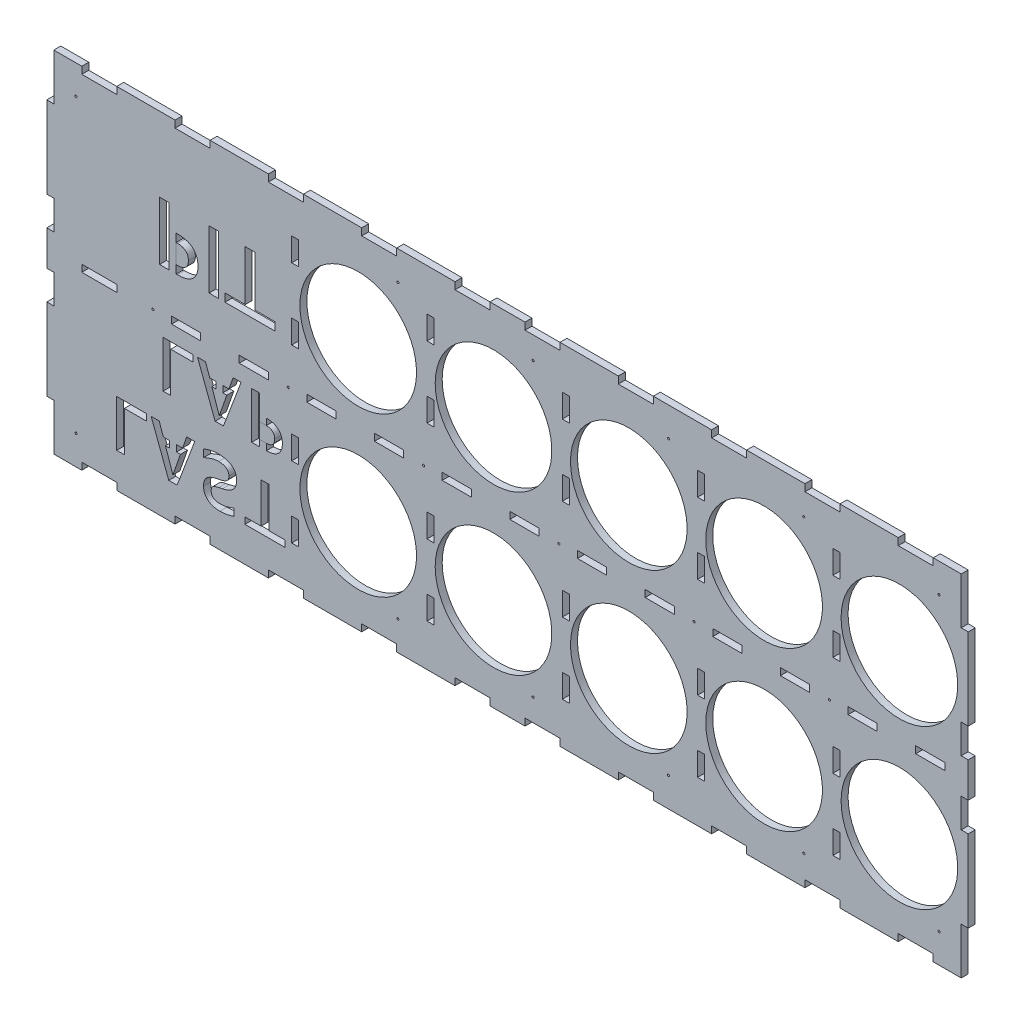
SolidWorks part; units mm, degrees
material "Acrylic (Medium-high impact)"
ref_plane "Front Plane" through (0, 0, 0) normal (0, 0, 1) x (1, 0, 0)
ref_plane "Top Plane" through (0, 0, 0) normal (0, 1, 0) x (1, 0, 0)
ref_plane "Right Plane" through (0, 0, 0) normal (1, 0, 0) x (0, 0, -1)
sketch "Sketch1" plane through (0, 0, 0) normal (0, 0, 1) x (1, 0, 0)
  line L1 (395, 150) -> (-395, 150)
  line L2 (395, 150) -> (395, -150)
  line L3 (395, -150) -> (-395, -150)
  line L4 (-395, 150) -> (-395, -150)
  line L5 (395, 150) -> (-395, -150) construction
  line L6 (395, -150) -> (-395, 150) construction
  point P0 (0, 0)
  dimension "D1" = 790
  dimension "D2" = 300
extrude "Boss-Extrude1" add sketch "Sketch1" along normal blind 6
sketch "Sketch2" plane through (0, 0, 0) normal (0, 0, -1) x (-1, 0, 0)
  line L0 (364.5528, -80.2188) -> (191, -80.2188) construction
  line L2 (191, -133) -> (191, -7) construction
  line L3 (304.6049, 86.1379) -> (205.3374, 86.1379) construction
  circle A0 centre (-336, -70) radius 50
  circle A1 centre (-220, -70) radius 50
  circle A2 centre (-220, 66) radius 50
  circle A3 centre (-336, 66) radius 50
  circle A4 centre (-104, -70) radius 50
  circle A5 centre (-104, 66) radius 50
  circle A6 centre (12, -70) radius 50
  circle A7 centre (12, 66) radius 50
  circle A8 centre (128, -70) radius 50
  circle A9 centre (128, 66) radius 50
  text T0 "<b>LAST</b>\r\n<b>LAP</b>" font "SOLIDWORKS GDT" height 40
  text T1 "<b>PIT</b>" font "SOLIDWORKS GDT" height 50
  point P0 (-336, 66)
  point P2 (-336, -70)
  point P4 (-220, 66)
  point P6 (-220, -70)
  dimension "D1" = 100
  dimension "D2" = 5
extrude "Cut-Extrude1" cut sketch "Sketch2" against normal blind 10
sketch "Sketch3" plane through (0, 0, 0) normal (0, 0, -1) x (-1, 0, 0)
  line L0 (286.8584, -120.2188) -> (286.8584, -77.9983) construction
  line L1 (290.4225, -120.2188) -> (283.2943, -120.2188) construction
  line L2 (247.1116, -56.4213) -> (247.1116, -7.6896) construction
  line L3 (250.6756, -56.4213) -> (243.5475, -56.4213) construction
  line L4 (290.0479, 66.5177) -> (290.0479, 86.1379) construction
  line L5 (283.8584, -100.0307) -> (289.8584, -100.0307)
  line L6 (283.8584, -100.0307) -> (283.8584, -87.3624)
  line L7 (283.8584, -87.3624) -> (289.8584, -87.3624)
  line L8 (289.8584, -100.0307) -> (289.8584, -87.3624)
  line L9 (283.8584, -100.0307) -> (289.8584, -87.3624) construction
  line L10 (283.8584, -87.3624) -> (289.8584, -100.0307) construction
  line L11 (244.1116, -36.3269) -> (250.1116, -36.3269)
  line L12 (244.1116, -36.3269) -> (244.1116, -13.8977)
  line L13 (244.1116, -13.8977) -> (250.1116, -13.8977)
  line L14 (250.1116, -36.3269) -> (250.1116, -13.8977)
  line L15 (244.1116, -36.3269) -> (250.1116, -13.8977) construction
  line L16 (244.1116, -13.8977) -> (250.1116, -36.3269) construction
  line L17 (290.0479, 81.5454) -> (284.0479, 81.5454)
  line L18 (290.0479, 81.5454) -> (290.0479, 32.0485)
  line L19 (290.0479, 32.0485) -> (284.0479, 32.0485)
  line L20 (284.0479, 81.5454) -> (284.0479, 32.0485)
  line L21 (212.7722, -32.1175) -> (212.7722, -16.4213) construction
  line L22 (212.7722, -27.2579) -> (206.7722, -27.2579)
  line L23 (212.7722, -27.2579) -> (212.7722, -59.8105)
  line L24 (212.7722, -59.8105) -> (206.7722, -59.8105)
  line L25 (206.7722, -27.2579) -> (206.7722, -59.8105)
  point P8 (286.8584, -93.6965)
  point P13 (247.1116, -25.1123)
  dimension "D1" = 6
extrude "Boss-Extrude2" add sketch "Sketch3" against normal up to surface (6 mm away)
sketch "Sketch4" plane through (0, 0, 0) normal (0, 0, -1) x (-1, 0, 0)
  line L0 (-395, -150) -> (-395, 150) construction
  line L1 (-395, -150) -> (-389, -150)
  line L2 (-395, -150) -> (-395, -110)
  line L3 (-395, -110) -> (-389, -110)
  line L4 (-389, -150) -> (-389, -110)
  line L5 (-395, 150) -> (395, 150) construction
  line L6 (-395, -40) -> (-389, -40)
  line L7 (-395, -40) -> (-395, -15)
  line L8 (-389, -15) -> (-395, -15)
  line L9 (-389, -40) -> (-389, -15)
  line L10 (-45, 150) -> (-45, 144)
  line L11 (0, 76.0027) -> (0, 0) construction
  line L12 (0, 0) -> (-103.2, 0) construction
  line L13 (-389, 40) -> (-389, 15)
  line L14 (-389, 15) -> (-395, 15)
  line L15 (-395, 40) -> (-395, 15)
  line L16 (-395, 40) -> (-389, 40)
  line L17 (-389, 150) -> (-389, 110)
  line L18 (-45, 150) -> (-15, 150)
  line L19 (-395, 110) -> (-389, 110)
  line L20 (-45, 144) -> (-15, 144)
  line L21 (-15, 150) -> (-15, 144)
  line L22 (395, -150) -> (-395, -150) construction
  line L23 (-395, 150) -> (-395, 110)
  line L24 (-395, 150) -> (-389, 150)
  line L25 (395, 150) -> (389, 150)
  line L26 (395, 150) -> (395, 110)
  line L27 (395, 110) -> (389, 110)
  line L28 (389, 150) -> (389, 110)
  line L29 (395, 40) -> (389, 40)
  line L30 (395, 40) -> (395, 15)
  line L31 (389, 15) -> (395, 15)
  line L32 (389, 40) -> (389, 15)
  line L33 (389, -40) -> (389, -15)
  line L34 (389, -15) -> (395, -15)
  line L35 (395, -40) -> (395, -15)
  line L36 (395, -40) -> (389, -40)
  line L37 (389, -150) -> (389, -110)
  line L38 (395, -110) -> (389, -110)
  line L39 (395, -150) -> (395, -110)
  line L40 (395, -150) -> (389, -150)
  line L41 (-125, 150) -> (-125, 144)
  line L42 (-125, 150) -> (-95, 150)
  line L43 (-125, 144) -> (-95, 144)
  line L44 (-95, 150) -> (-95, 144)
  line L45 (-205, 150) -> (-205, 144)
  line L46 (-205, 150) -> (-175, 150)
  line L47 (-205, 144) -> (-175, 144)
  line L48 (-175, 150) -> (-175, 144)
  line L49 (-285, 150) -> (-285, 144)
  line L50 (-285, 150) -> (-255, 150)
  line L51 (-285, 144) -> (-255, 144)
  line L52 (-255, 150) -> (-255, 144)
  line L53 (-365, 150) -> (-365, 144)
  line L54 (-365, 150) -> (-335, 150)
  line L55 (-365, 144) -> (-335, 144)
  line L56 (-335, 150) -> (-335, 144)
  line L57 (335, 150) -> (335, 144)
  line L58 (365, 144) -> (335, 144)
  line L59 (365, 150) -> (335, 150)
  line L60 (365, 150) -> (365, 144)
  line L61 (255, 150) -> (255, 144)
  line L62 (285, 144) -> (255, 144)
  line L63 (285, 150) -> (255, 150)
  line L64 (285, 150) -> (285, 144)
  line L65 (175, 150) -> (175, 144)
  line L66 (205, 144) -> (175, 144)
  line L67 (205, 150) -> (175, 150)
  line L68 (205, 150) -> (205, 144)
  line L69 (95, 150) -> (95, 144)
  line L70 (125, 144) -> (95, 144)
  line L71 (125, 150) -> (95, 150)
  line L72 (125, 150) -> (125, 144)
  line L73 (15, 150) -> (15, 144)
  line L74 (45, 144) -> (15, 144)
  line L75 (45, 150) -> (15, 150)
  line L76 (45, 150) -> (45, 144)
  line L77 (45, -150) -> (45, -144)
  line L78 (45, -150) -> (15, -150)
  line L79 (45, -144) -> (15, -144)
  line L80 (15, -150) -> (15, -144)
  line L81 (125, -150) -> (125, -144)
  line L82 (125, -150) -> (95, -150)
  line L83 (125, -144) -> (95, -144)
  line L84 (95, -150) -> (95, -144)
  line L85 (205, -150) -> (205, -144)
  line L86 (205, -150) -> (175, -150)
  line L87 (205, -144) -> (175, -144)
  line L88 (175, -150) -> (175, -144)
  line L89 (285, -150) -> (285, -144)
  line L90 (285, -150) -> (255, -150)
  line L91 (285, -144) -> (255, -144)
  line L92 (255, -150) -> (255, -144)
  line L93 (365, -150) -> (365, -144)
  line L94 (365, -150) -> (335, -150)
  line L95 (365, -144) -> (335, -144)
  line L96 (335, -150) -> (335, -144)
  line L97 (-335, -150) -> (-335, -144)
  line L98 (-365, -144) -> (-335, -144)
  line L99 (-365, -150) -> (-335, -150)
  line L100 (-365, -150) -> (-365, -144)
  line L101 (-255, -150) -> (-255, -144)
  line L102 (-285, -144) -> (-255, -144)
  line L103 (-285, -150) -> (-255, -150)
  line L104 (-285, -150) -> (-285, -144)
  line L105 (-175, -150) -> (-175, -144)
  line L106 (-205, -144) -> (-175, -144)
  line L107 (-205, -150) -> (-175, -150)
  line L108 (-205, -150) -> (-205, -144)
  line L109 (-95, -150) -> (-95, -144)
  line L110 (-125, -144) -> (-95, -144)
  line L111 (-125, -150) -> (-95, -150)
  line L112 (-125, -150) -> (-125, -144)
  line L113 (-15, -150) -> (-15, -144)
  line L114 (-45, -144) -> (-15, -144)
  line L115 (-45, -150) -> (-15, -150)
  line L116 (-45, -150) -> (-45, -144)
  dimension "D1" = 40
  dimension "D2" = 25
  dimension "D3" = 6
  dimension "D4" = 110
  dimension "D5" = 15
  dimension "D6" = 30
  dimension "D7" = 5
extrude "Cut-Extrude2" cut sketch "Sketch4" against normal blind 6
sketch "Sketch5" plane through (0, 0, 0) normal (0, 0, -1) x (-1, 0, 0)
  line L0 (-279, 114) -> (-279, 94) construction
  line L1 (-279, 94) -> (-285, 94) construction
  line L2 (-285, 94) -> (-285, 114) construction
  line L3 (-285, 114) -> (-279, 114) construction
  line L4 (-279, 53) -> (-279, 33) construction
  line L5 (-279, 33) -> (-285, 33) construction
  line L6 (-285, 33) -> (-285, 53) construction
  line L7 (-285, 53) -> (-279, 53) construction
  line L8 (-279, -33) -> (-279, -53) construction
  line L9 (-279, -53) -> (-285, -53) construction
  line L10 (-285, -53) -> (-285, -33) construction
  line L11 (-285, -33) -> (-279, -33) construction
  line L12 (-279, -94) -> (-279, -114) construction
  line L13 (-279, -114) -> (-285, -114) construction
  line L14 (-285, -114) -> (-285, -94) construction
  line L15 (-285, -94) -> (-279, -94) construction
  line L16 (-279, 114) -> (-279, 94)
  line L17 (-279, 94) -> (-285, 94)
  line L18 (-285, 94) -> (-285, 114)
  line L19 (-285, 114) -> (-279, 114)
  line L20 (-279, 53) -> (-279, 33)
  line L21 (-279, 33) -> (-285, 33)
  line L22 (-285, 33) -> (-285, 53)
  line L23 (-285, 53) -> (-279, 53)
  line L24 (-279, -33) -> (-279, -53)
  line L25 (-279, -53) -> (-285, -53)
  line L26 (-285, -53) -> (-285, -33)
  line L27 (-285, -33) -> (-279, -33)
  line L28 (-279, -94) -> (-279, -114)
  line L29 (-279, -114) -> (-285, -114)
  line L30 (-285, -114) -> (-285, -94)
  line L31 (-285, -94) -> (-279, -94)
  line L32 (-350, 3) -> (-350, -3) construction
  line L33 (-375, 3) -> (-350, 3) construction
  line L34 (-350, -3) -> (-375, -3) construction
  line L35 (-375, -3) -> (-375, 3) construction
  line L36 (-350, 3) -> (-350, -3)
  line L37 (-375, 3) -> (-350, 3)
  line L38 (-350, -3) -> (-375, -3)
  line L39 (-375, -3) -> (-375, 3)
  line L40 (365, -3) -> (365, 3) construction
  line L41 (365, -3) -> (365, 3)
  line L42 (335, 3) -> (335, -3) construction
  line L43 (335, 3) -> (335, -3)
  line L44 (335, 3) -> (365, 3)
  line L45 (335, -3) -> (365, -3)
  line L46 (-163, 114) -> (-163, 94)
  line L47 (-163, 94) -> (-169, 94)
  line L48 (-169, 94) -> (-169, 114)
  line L49 (-169, 114) -> (-163, 114)
  line L50 (-163, 53) -> (-163, 33)
  line L51 (-163, 33) -> (-169, 33)
  line L52 (-169, 33) -> (-169, 53)
  line L53 (-169, 53) -> (-163, 53)
  line L54 (-163, -33) -> (-163, -53)
  line L55 (-163, -53) -> (-169, -53)
  line L56 (-169, -53) -> (-169, -33)
  line L57 (-169, -33) -> (-163, -33)
  line L58 (-163, -94) -> (-163, -114)
  line L59 (-163, -114) -> (-169, -114)
  line L60 (-169, -114) -> (-169, -94)
  line L61 (-169, -94) -> (-163, -94)
  line L62 (-47, 114) -> (-47, 94)
  line L63 (-47, 94) -> (-53, 94)
  line L64 (-53, 94) -> (-53, 114)
  line L65 (-53, 114) -> (-47, 114)
  line L66 (-47, 53) -> (-47, 33)
  line L67 (-47, 33) -> (-53, 33)
  line L68 (-53, 33) -> (-53, 53)
  line L69 (-53, 53) -> (-47, 53)
  line L70 (-47, -33) -> (-47, -53)
  line L71 (-47, -53) -> (-53, -53)
  line L72 (-53, -53) -> (-53, -33)
  line L73 (-53, -33) -> (-47, -33)
  line L74 (-47, -94) -> (-47, -114)
  line L75 (-47, -114) -> (-53, -114)
  line L76 (-53, -114) -> (-53, -94)
  line L77 (-53, -94) -> (-47, -94)
  line L78 (69, 114) -> (69, 94)
  line L79 (69, 94) -> (63, 94)
  line L80 (63, 94) -> (63, 114)
  line L81 (63, 114) -> (69, 114)
  line L82 (69, 53) -> (69, 33)
  line L83 (69, 33) -> (63, 33)
  line L84 (63, 33) -> (63, 53)
  line L85 (63, 53) -> (69, 53)
  line L86 (69, -33) -> (69, -53)
  line L87 (69, -53) -> (63, -53)
  line L88 (63, -53) -> (63, -33)
  line L89 (63, -33) -> (69, -33)
  line L90 (69, -94) -> (69, -114)
  line L91 (69, -114) -> (63, -114)
  line L92 (63, -114) -> (63, -94)
  line L93 (63, -94) -> (69, -94)
  line L94 (185, 114) -> (185, 94)
  line L95 (185, 94) -> (179, 94)
  line L96 (179, 94) -> (179, 114)
  line L97 (179, 114) -> (185, 114)
  line L98 (185, 53) -> (185, 33)
  line L99 (185, 33) -> (179, 33)
  line L100 (179, 33) -> (179, 53)
  line L101 (179, 53) -> (185, 53)
  line L102 (185, -33) -> (185, -53)
  line L103 (185, -53) -> (179, -53)
  line L104 (179, -53) -> (179, -33)
  line L105 (179, -33) -> (185, -33)
  line L106 (185, -94) -> (185, -114)
  line L107 (185, -114) -> (179, -114)
  line L108 (179, -114) -> (179, -94)
  line L109 (179, -94) -> (185, -94)
  line L110 (-292, 3) -> (-292, -3)
  line L111 (-317, 3) -> (-292, 3)
  line L112 (-292, -3) -> (-317, -3)
  line L113 (-317, -3) -> (-317, 3)
  line L114 (-234, 3) -> (-234, -3)
  line L115 (-259, 3) -> (-234, 3)
  line L116 (-234, -3) -> (-259, -3)
  line L117 (-259, -3) -> (-259, 3)
  line L118 (-176, 3) -> (-176, -3)
  line L119 (-201, 3) -> (-176, 3)
  line L120 (-176, -3) -> (-201, -3)
  line L121 (-201, -3) -> (-201, 3)
  line L122 (-118, 3) -> (-118, -3)
  line L123 (-143, 3) -> (-118, 3)
  line L124 (-118, -3) -> (-143, -3)
  line L125 (-143, -3) -> (-143, 3)
  line L126 (-60, 3) -> (-60, -3)
  line L127 (-85, 3) -> (-60, 3)
  line L128 (-60, -3) -> (-85, -3)
  line L129 (-85, -3) -> (-85, 3)
  line L130 (-2, 3) -> (-2, -3)
  line L131 (-27, 3) -> (-2, 3)
  line L132 (-2, -3) -> (-27, -3)
  line L133 (-27, -3) -> (-27, 3)
  line L134 (56, 3) -> (56, -3)
  line L135 (31, 3) -> (56, 3)
  line L136 (56, -3) -> (31, -3)
  line L137 (31, -3) -> (31, 3)
  line L138 (114, 3) -> (114, -3)
  line L139 (89, 3) -> (114, 3)
  line L140 (114, -3) -> (89, -3)
  line L141 (89, -3) -> (89, 3)
  line L142 (172, 3) -> (172, -3)
  line L143 (147, 3) -> (172, 3)
  line L144 (172, -3) -> (147, -3)
  line L145 (147, -3) -> (147, 3)
  line L146 (230, 3) -> (230, -3)
  line L147 (205, 3) -> (230, 3)
  line L148 (230, -3) -> (205, -3)
  line L149 (205, -3) -> (205, 3)
  line L150 (288, 3) -> (288, -3)
  line L151 (263, 3) -> (288, 3)
  line L152 (288, -3) -> (263, -3)
  line L153 (263, -3) -> (263, 3)
  dimension "D1" = 5
  dimension "D2" = 12
extrude "Cut-Extrude3" cut sketch "Sketch5" against normal blind 6
sketch "Sketch6" plane through (0, 0, 0) normal (0, 0, -1) x (-1, 0, 0)
  line L0 (0, -48.5152) -> (0, 0) construction
  line L1 (0, 0) -> (-427.9385, 0) construction
  circle A0 centre (-370, -125) radius 0.9
  circle A1 centre (-370, 125) radius 0.9
  circle A2 centre (-254, -125) radius 0.9
  circle A3 centre (-254, 125) radius 0.9
  circle A4 centre (-138, -125) radius 0.9
  circle A5 centre (-138, 125) radius 0.9
  circle A6 centre (-22, -125) radius 0.9
  circle A7 centre (-22, 125) radius 0.9
  circle A8 centre (94, -125) radius 0.9
  circle A9 centre (94, 125) radius 0.9
  circle A10 centre (370, 125) radius 0.9
  circle A11 centre (370, -125) radius 0.9
  circle A12 centre (-276, 0) radius 0.9
  circle A13 centre (-160, 0) radius 0.9
  circle A14 centre (-44, 0) radius 0.9
  circle A15 centre (72, 0) radius 0.9
  circle A16 centre (188, 0) radius 0.9
  circle A17 centre (304, 0) radius 0.9
  dimension "D1" = 125
  dimension "D3" = 1.8
  dimension "D5" = 276
  dimension "D2" = 370
  dimension "D4" = 5
  dimension "D6" = 6
extrude "Cut-Extrude4" cut sketch "Sketch6" against normal blind 10
